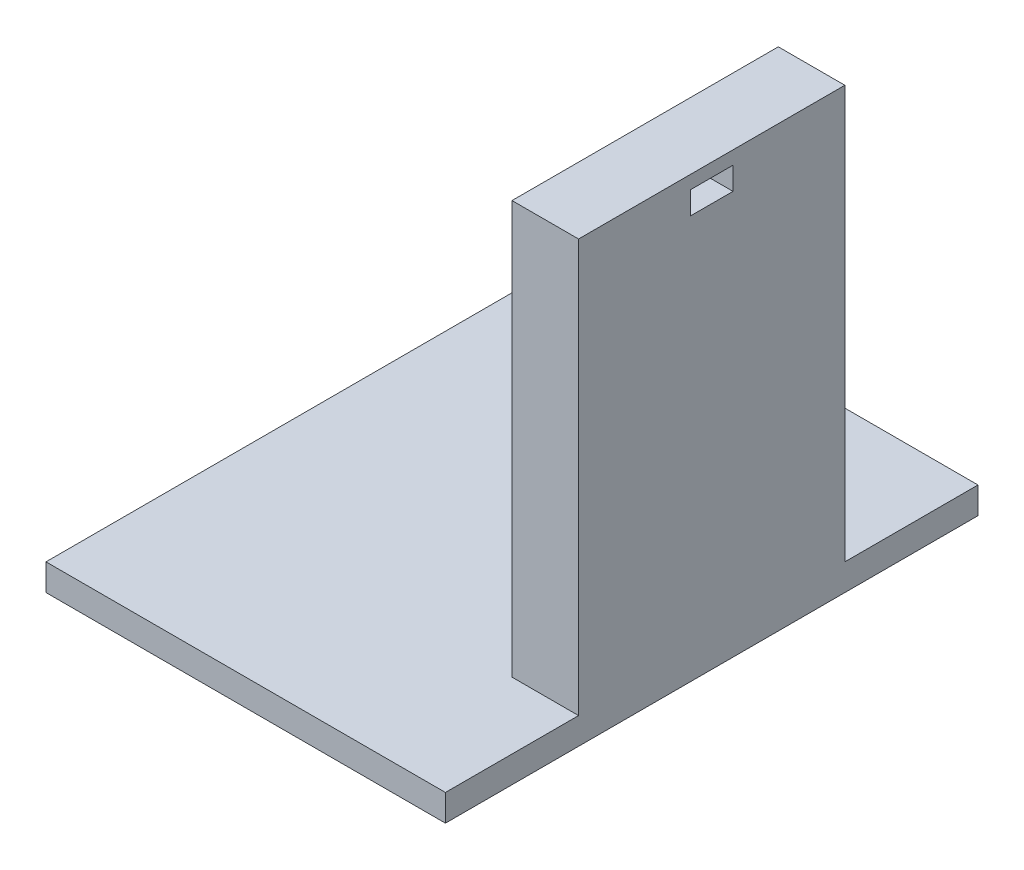
SolidWorks part; units mm, degrees
ref_plane "Plan de face" through (0, 0, 0) normal (0, 0, 1) x (1, 0, 0)
ref_plane "Plan de dessus" through (0, 0, 0) normal (0, 1, 0) x (1, 0, 0)
ref_plane "Plan de droite" through (0, 0, 0) normal (1, 0, 0) x (0, 0, -1)
sketch "Esquisse2" plane through (0, 0, 0) normal (0, 1, 0) x (1, 0, 0)
  line L0 (54.6919, 181.7) -> (54.6919, -18.3)
  line L1 (-95.3081, 181.7) -> (54.6919, 181.7)
  line L2 (-95.3081, 181.7) -> (-95.3081, -18.3)
  line L3 (-95.3081, -18.3) -> (54.6919, -18.3)
extrude "Boss.-Extru.6" add sketch "Esquisse2" along normal blind 10
sketch "Esquisse4" plane through (0, 0, 0) normal (0, 1, 0) x (1, 0, 0)
  line L0 (29.6919, 31.7) -> (54.6919, 31.7)
  line L1 (29.6919, 31.7) -> (29.6919, 131.7)
  line L2 (29.6919, 131.7) -> (54.6919, 131.7)
  line L3 (54.6919, 31.7) -> (54.6919, 131.7)
  line L4 (54.6919, -18.3) -> (54.6919, 181.7) construction
  line L5 (54.6919, -18.3) -> (54.6919, 181.7)
extrude "Boss.-Extru.7" add sketch "Esquisse4" along normal blind 160 contours L0 L3 L2 L1 region at (42.1919, 0, -81.7)
sketch "Esquisse8" plane through (29.6919, 0, 0) normal (-1, 0, 0) x (0, 0, 1)
  line L0 (-93.9, 139.9717) -> (-69.5, 139.9717)
  line L1 (-93.9, 139.9717) -> (-93.9, 160)
  line L2 (-93.9, 160) -> (-69.5, 160)
  line L3 (-69.5, 139.9717) -> (-69.5, 160)
  line L4 (-31.7, 160) -> (-131.7, 160) construction
  point P6 (-81.7, 160)
  dimension "D1" = 20.0283
  dimension "D2" = 24.4
extrude "Enlèv. mat.-Extru.1" cut sketch "Esquisse8" against normal blind 12.2
sketch "Esquisse9" plane through (41.8919, 0, 0) normal (-1, 0, 0) x (0, 0, 1)
  line L0 (-87.7, 158.4859) -> (-87.7, 153.4859) construction
  line L1 (-87.7, 153.4859) -> (-75.7, 153.4859) construction
  line L2 (-75.7, 153.4859) -> (-75.7, 158.4859) construction
  line L3 (-75.7, 158.4859) -> (-87.7, 158.4859) construction
  line L4 (-81.7, 160) -> (-81.7, 158.4859) construction
  line L6 (-69.5, 160) -> (-93.9, 160) construction
  line L7 (-87.7, 158.4859) -> (-87.7, 153.4859)
  line L8 (-87.7, 153.4859) -> (-75.7, 153.4859)
  line L9 (-75.7, 153.4859) -> (-75.7, 158.4859)
  line L10 (-75.7, 158.4859) -> (-87.7, 158.4859)
  point P6 (-81.7, 158.4859)
  dimension "D1" = 1.5141
  dimension "D2" = 5
  dimension "D3" = 12
extrude "Enlèv. mat.-Extru.2" cut sketch "Esquisse9" against normal blind 42.2
sketch "Esquisse11" plane through (41.8919, 0, 0) normal (-1, 0, 0) x (0, 0, 1)
  line L0 (-69.5, 160) -> (-93.9, 160) construction
  line L1 (-89.7, 160) -> (-73.7, 160)
  line L2 (-89.7, 160) -> (-89.7, 151.4859)
  line L3 (-89.7, 151.4859) -> (-73.7, 151.4859)
  line L4 (-73.7, 160) -> (-73.7, 151.4859)
  line L5 (-87.7, 155.7429) -> (-89.7, 155.7429) construction
  line L6 (-87.7, 158.4859) -> (-87.7, 153.4859) construction
  line L7 (-75.7, 155.9859) -> (-73.7, 155.9859) construction
  line L8 (-75.7, 153.4859) -> (-75.7, 158.4859) construction
  line L9 (-81.7, 153.4859) -> (-81.7, 151.4859) construction
  line L10 (-87.7, 153.4859) -> (-75.7, 153.4859) construction
  dimension "D1" = 2
  dimension "D2" = 2
  dimension "D3" = 2
extrude "Enlèv. mat.-Extru.3" cut sketch "Esquisse11" against normal blind 42.2
sketch "Esquisse12" plane through (29.6919, 0, 0) normal (-1, 0, 0) x (0, 0, 1)
  line L0 (-94.4, 160) -> (-94.4, 139.97)
  line L1 (-93.9, 160) -> (-131.7, 160) construction
  line L3 (-69, 139.97) -> (-69, 160)
  line L4 (-31.7, 160) -> (-69.5, 160) construction
  line L5 (-69, 160) -> (-69.5, 160)
  line L6 (-69.5, 160) -> (-69.5, 139.9717)
  line L8 (-93.9, 139.9717) -> (-93.9, 160)
  line L9 (-93.9, 160) -> (-94.4, 160)
  line L10 (-79.5159, 139.9717) -> (-79.5159, 139.4717) construction
  line L11 (-69, 139.97) -> (-69.5, 139.9717)
  line L13 (-93.9, 139.9717) -> (-94.4, 139.97)
  dimension "D1" = 0.5
  dimension "D2" = 0.5
  dimension "D3" = 20.0283
  dimension "D4" = 20.03
  dimension "D5" = 20.03
extrude "Enlèv. mat.-Extru.6" cut sketch "Esquisse12" against normal blind 12.2
sketch "Esquisse13" plane through (0, 160, 0) normal (0, 1, 0) x (1, 0, 0)
  line L1 (29.6919, 131.7) -> (54.6919, 131.7)
  line L2 (29.6919, 131.7) -> (29.6919, 31.7)
  line L3 (29.6919, 31.7) -> (54.6919, 31.7)
  line L4 (54.6919, 131.7) -> (54.6919, 31.7)
extrude "Boss.-Extru.8" add sketch "Esquisse13" along normal blind 5
sketch "Esquisse14" plane through (29.6919, 0, 0) normal (-1, 0, 0) x (0, 0, 1)
  line L0 (-94.4, 160) -> (-94.4, 160.5)
  line L2 (-94.4, 160) -> (-69, 160)
  line L4 (-69, 160) -> (-69, 160.5)
  line L5 (-69, 160.5) -> (-94.4, 160.5)
  dimension "D1" = 0.5
extrude "Enlèv. mat.-Extru.7" cut sketch "Esquisse14" against normal blind 12.2
